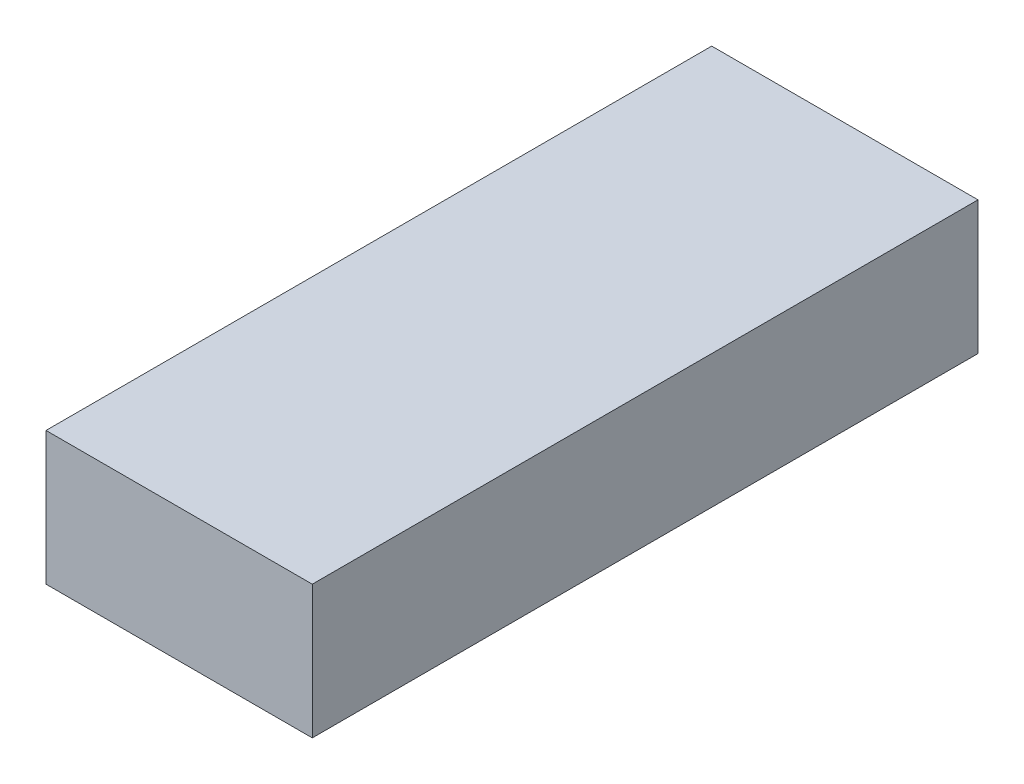
SolidWorks part; units mm, degrees
ref_plane "Front Plane" through (0, 0, 0) normal (0, 0, 1) x (1, 0, 0)
ref_plane "Top Plane" through (0, 0, 0) normal (0, 1, 0) x (1, 0, 0)
ref_plane "Right Plane" through (0, 0, 0) normal (1, 0, 0) x (0, 0, -1)
sketch "Sketch1" plane through (0, 0, 0) normal (0, 1, 0) x (1, 0, 0)
  line L1 (0, 0) -> (20, 0)
  line L2 (0, 0) -> (0, 50)
  line L3 (0, 50) -> (20, 50)
  line L4 (20, 0) -> (20, 50)
  dimension "D1" = 50
  dimension "D2" = 20
extrude "Boss-Extrude1" add sketch "Sketch1" along normal blind 10
